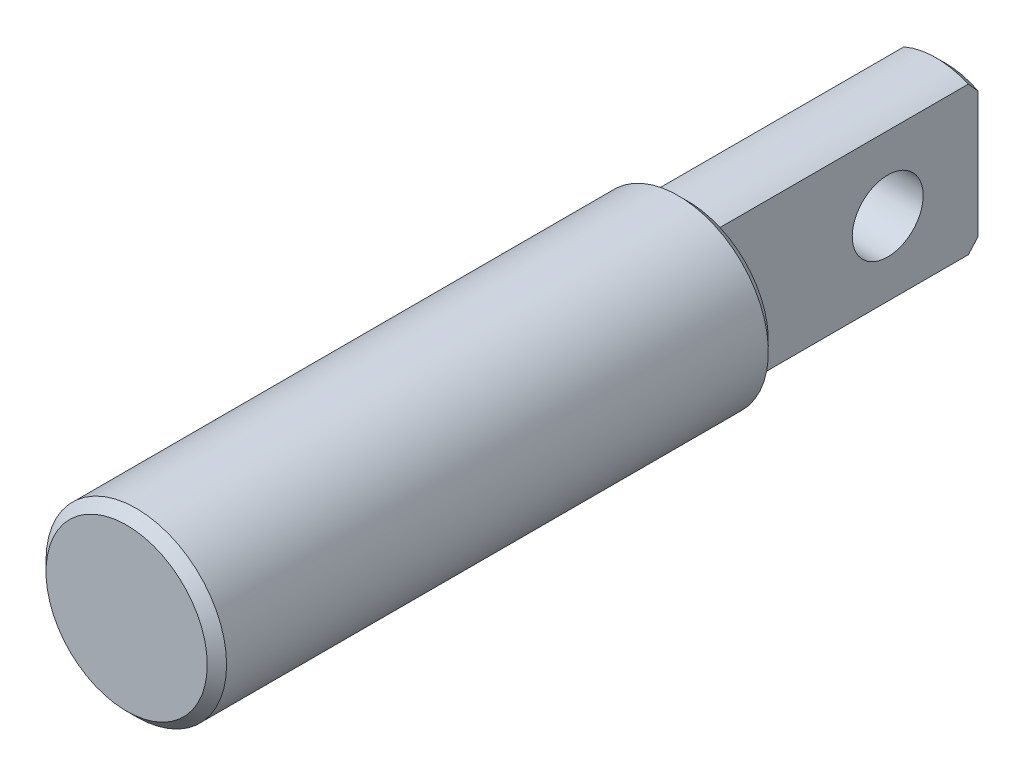
SolidWorks part; units mm, degrees
ref_plane "Plan de face" through (0, 0, 0) normal (0, 0, 1) x (1, 0, 0)
ref_plane "Plan de dessus" through (0, 0, 0) normal (0, 1, 0) x (1, 0, 0)
ref_plane "Plan de droite" through (0, 0, 0) normal (1, 0, 0) x (0, 0, -1)
sketch "Esquisse1" plane through (0, 0, 0) normal (0, 0, 1) x (1, 0, 0)
  circle A0 centre (0, 0) radius 14
  dimension "D1" = 28
extrude "Extrusion1" add sketch "Esquisse1" along normal blind 127
chamfer "Chanfrein1" distance 1.5 angle 45 1 edges at (14, 0, 127)
sketch "Esquisse2" plane through (0, 0, 0) normal (0, 0, -1) x (-1, 0, 0)
  circle A0 centre (0, 0) radius 12.5
  dimension "D1" = 25
extrude "Enlèv. mat.-Extru.1" cut sketch "Esquisse2" against normal blind 40 flip side to cut
sketch "Esquisse3" plane through (0, 0, 0) normal (0, 0, 1) x (1, 0, 0)
  line L0 (0, 0) -> (0, 14.3092) construction
  line L1 (-5, 14.4189) -> (5, 14.4189)
  line L2 (-5, 14.4189) -> (-5, -13.761)
  line L3 (-5, -13.761) -> (5, -13.761)
  line L4 (5, 14.4189) -> (5, -13.761)
  dimension "D1" = 10
extrude "Enlèv. mat.-Extru.2" cut sketch "Esquisse3" along normal blind 40 flip side to cut
chamfer "Chanfrein2" distance 1.5 angle 45 2 edges at (0, 12.5, 0) (0, -12.5, 0)
chamfer "Chanfrein3" distance 1.5 angle 45 1 edges at (-14, 0, 40)
sketch "Esquisse4" plane through (-5, 0, 0) normal (-1, 0, 0) x (0, 0, 1)
  line L0 (0, 9.798) -> (0, -9.798) construction
  circle A0 centre (14, 0) radius 5.5
  dimension "D2" = 11
  dimension "D1" = 14
extrude "Enlèv. mat.-Extru.3" cut sketch "Esquisse4" against normal blind 23
